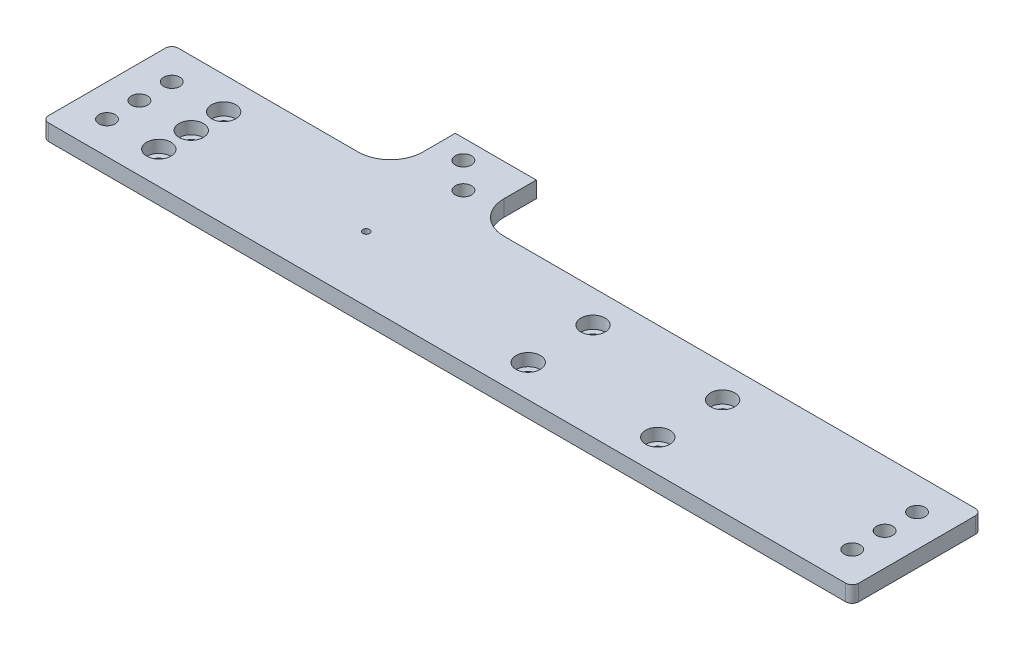
SolidWorks part; units mm, degrees
material "6061-T6 (SS)"
ref_plane "Front" through (0, 0, 0) normal (0, 0, 1) x (1, 0, 0)
ref_plane "Top" through (0, 0, 0) normal (0, 1, 0) x (1, 0, 0)
ref_plane "Right" through (0, 0, 0) normal (1, 0, 0) x (0, 0, -1)
sketch "Sketch1" plane through (0, 0, 0) normal (0, 1, 0) x (1, 0, 0)
  line L1 (-158.75, -25.4) -> (158.75, -25.4)
  line L2 (-158.75, -25.4) -> (-158.75, 25.4)
  line L3 (-158.75, 25.4) -> (158.75, 25.4)
  line L4 (158.75, -25.4) -> (158.75, 25.4)
  line L5 (-158.75, -25.4) -> (158.75, 25.4) construction
  line L6 (-158.75, 25.4) -> (158.75, -25.4) construction
  point P0 (0, 0)
  dimension "D1" = 50.8
  dimension "D2" = 317.5
extrude "Boss-Extrude1" add sketch "Sketch1" along normal blind 6.35
hole_wizard "CBORE for #10 Socket Head Cap Screw1" positions "Sketch2" profile "Sketch4" counterbore size "#10" standard "ANSI Inch" end condition through all
sketch "Sketch2" plane through (0, 6.35, 0) normal (0, 1, 0) x (1, 0, 0)
  line L2 (158.75, 25.4) -> (-158.75, 25.4) construction
  line L6 (-158.75, -25.4) -> (158.75, -25.4) construction
  line L8 (-158.75, 25.4) -> (-158.75, -25.4) construction
  line L12 (158.75, -25.4) -> (158.75, 25.4) construction
  line L15 (19.05, 12.7) -> (19.05, 25.4) construction
  line L17 (19.05, -12.7) -> (19.05, -25.4) construction
  line L18 (-125.73, -25.4) -> (-125.73, -12.7) construction
  line L20 (-125.73, 0) -> (-125.73, 12.7) construction
  line L21 (-125.73, 12.7) -> (-125.73, 25.4) construction
  line L22 (-125.73, 0) -> (-125.73, -12.7) construction
  point P64 (19.05, 12.7)
  point P66 (69.85, 12.7)
  point P68 (19.05, -12.7)
  point P70 (69.85, -12.7)
  point P92 (-125.73, 12.7)
  point P94 (-125.73, 0)
  point P102 (-125.73, -12.7)
  dimension "D2" = 50.8
  dimension "D3" = 25.4
  dimension "D4" = 88.9
  dimension "D5" = 33.02
sketch "Sketch4" plane through (-125.73, 6.35, 12.7) normal (1, 0, 0) x (0, 0, 1)
  line L0 (0, 0) -> (0, 6.35)
  line L1 (0, 6.35) -> (2.5527, 6.35)
  line L3 (2.5527, 6.35) -> (2.5527, 4.826)
  line L4 (2.5527, 4.826) -> (4.7625, 4.826)
  line L5 (4.7625, 4.826) -> (4.7625, 0)
  line L7 (4.7625, 0) -> (0, 0)
  line L11 (0, -6.35) -> (0, 107.95) construction
  dimension "Thru Hole Dia." = 5.1054
  dimension "Thru Hole Depth" = 6.35
  dimension "C'Bore Dia." = 9.525
  dimension "C'Bore Depth" = 4.826
sketch "Sketch7" plane through (0, 0, 0) normal (0, -1, 0) x (1, 0, 0)
  line L0 (-146.05, 25.4) -> (-146.05, 12.7) construction
  line L1 (-158.75, 25.4) -> (158.75, 25.4) construction
  line L2 (-146.05, 12.7) -> (-146.05, 0) construction
  line L3 (-146.05, 0) -> (-146.05, -12.7) construction
  line L4 (-146.05, -12.7) -> (-146.05, -25.4) construction
  line L5 (158.75, -25.4) -> (-158.75, -25.4) construction
  line L7 (-158.75, -25.4) -> (-158.75, 25.4) construction
  line L8 (146.05, 25.4) -> (146.05, 12.7) construction
  line L9 (146.05, 12.7) -> (146.05, 0) construction
  line L10 (146.05, 0) -> (146.05, -12.7) construction
  line L11 (146.05, -12.7) -> (146.05, -25.4) construction
  line L13 (158.75, 25.4) -> (158.75, -25.4) construction
  point P0 (-146.05, 12.7)
  point P2 (-146.05, 0)
  point P4 (-146.05, -12.7)
  point P6 (146.05, 12.7)
  point P8 (146.05, 0)
  point P10 (146.05, -12.7)
  dimension "D1" = 12.7
  dimension "D2" = 12.7
hole_wizard "1/4 (0.25) Diameter Hole1" positions "Sketch7" profile "Sketch6" hole size "1/4" standard "ANSI Inch" end condition through all
sketch "Sketch6" plane through (-146.05, 0, 12.7) normal (1, 0, 0) x (0, 0, -1)
  line L0 (0, 0) -> (0, 6.35)
  line L1 (0, 6.35) -> (3.175, 6.35)
  line L2 (3.175, 6.35) -> (3.175, 0)
  line L5 (3.175, 0) -> (0, 0)
  line L11 (0, -6.35) -> (0, 107.95) construction
  dimension "Thru Hole Dia." = 6.35
  dimension "Thru Hole Depth" = 6.35
sketch "Sketch10" plane through (0, 0, 0) normal (0, -1, 0) x (-1, 0, 0)
  line L0 (158.75, 25.4) -> (158.75, -25.4) construction
  point P0 (57.15, 0)
  dimension "D1" = 101.6
hole_wizard "#6-32 Tapped Hole1" positions "Sketch10" profile "Sketch9" tap size "#6-32" standard "ANSI Inch" end condition through all
sketch "Sketch9" plane through (-57.15, 0, 0) normal (1, 0, 0) x (0, 0, -1)
  line L0 (0, 0) -> (0, 6.35)
  line L1 (0, 6.35) -> (1.3525, 6.35)
  line L2 (1.3525, 6.35) -> (1.3525, 0)
  line L5 (1.3525, 0) -> (0, 0)
  line L11 (0, -6.35) -> (0, 107.95) construction
  dimension "Thru Tap Drill Dia." = 2.7051
  dimension "Thru Tap Drill Depth" = 6.35
cosmetic thread "Hole Thread1" parameters "D2"=3.5052
sketch "Sketch11" plane through (0, 0, 0) normal (0, -1, 0) x (1, 0, 0)
  line L0 (158.75, -25.4) -> (-158.75, -25.4) construction
  line L1 (-70.0118, -25.4) -> (-48.1024, -25.4)
  line L2 (-70.0118, -25.4) -> (-70.0118, -45.81)
  line L3 (-70.0118, -45.81) -> (-48.1024, -45.81)
  line L4 (-48.1024, -25.4) -> (-48.1024, -45.81)
extrude "Boss-Extrude2" [suppressed] add sketch "Sketch11" against normal up to surface (6.35 mm away) up to face at (-57.15, 6.35, -1.3526)
sketch "Sketch12" plane through (0, 6.35, 0) normal (0, 1, 0) x (1, 0, 0)
  line L5 (-158.75, 25.4) -> (-158.75, -25.4) construction
  line L6 (-73.025, 25.4) -> (-73.025, 50.8)
  line L7 (158.75, 25.4) -> (-158.75, 25.4) construction
  line L8 (-73.025, 50.8) -> (-41.275, 50.8)
  line L9 (-41.275, 50.8) -> (-41.275, 25.4)
  line L10 (-73.025, 25.4) -> (-41.275, 25.4)
  dimension "D4" = 85.725
  dimension "D5" = 25.4
  dimension "D6" = 31.75
extrude "Boss-Extrude3" add sketch "Sketch12" against normal up to surface (6.35 mm away) up to face at (-57.15, 0, -1.3526)
sketch "Sketch15" plane through (0, 0, 0) normal (0, -1, 0) x (-1, 0, 0)
  point P0 (62.23, 43.18)
  point P3 (52.07, 33.02)
hole_wizard "1/4 (0.25) Diameter Hole2" positions "Sketch15" profile "Sketch14" hole size "1/4" standard "ANSI Inch" end condition through all
sketch "Sketch14" plane through (-62.23, 0, -43.18) normal (1, 0, 0) x (0, 0, -1)
  line L0 (0, 0) -> (0, 6.35)
  line L1 (0, 6.35) -> (3.175, 6.35)
  line L2 (3.175, 6.35) -> (3.175, 0)
  line L5 (3.175, 0) -> (0, 0)
  line L11 (0, -6.35) -> (0, 107.95) construction
  dimension "Thru Hole Dia." = 6.35
  dimension "Thru Hole Depth" = 6.35
fillet "Fillet1" radius 12.7 2 edges at (-41.275, 3.175, -25.4) (-73.025, 3.175, -25.4)
fillet "Fillet2" radius 2.54 4 edges at (158.75, 3.175, -25.4) (158.75, 3.175, 25.4) (-158.75, 3.175, 25.4) (-158.75, 3.175, -25.4)
